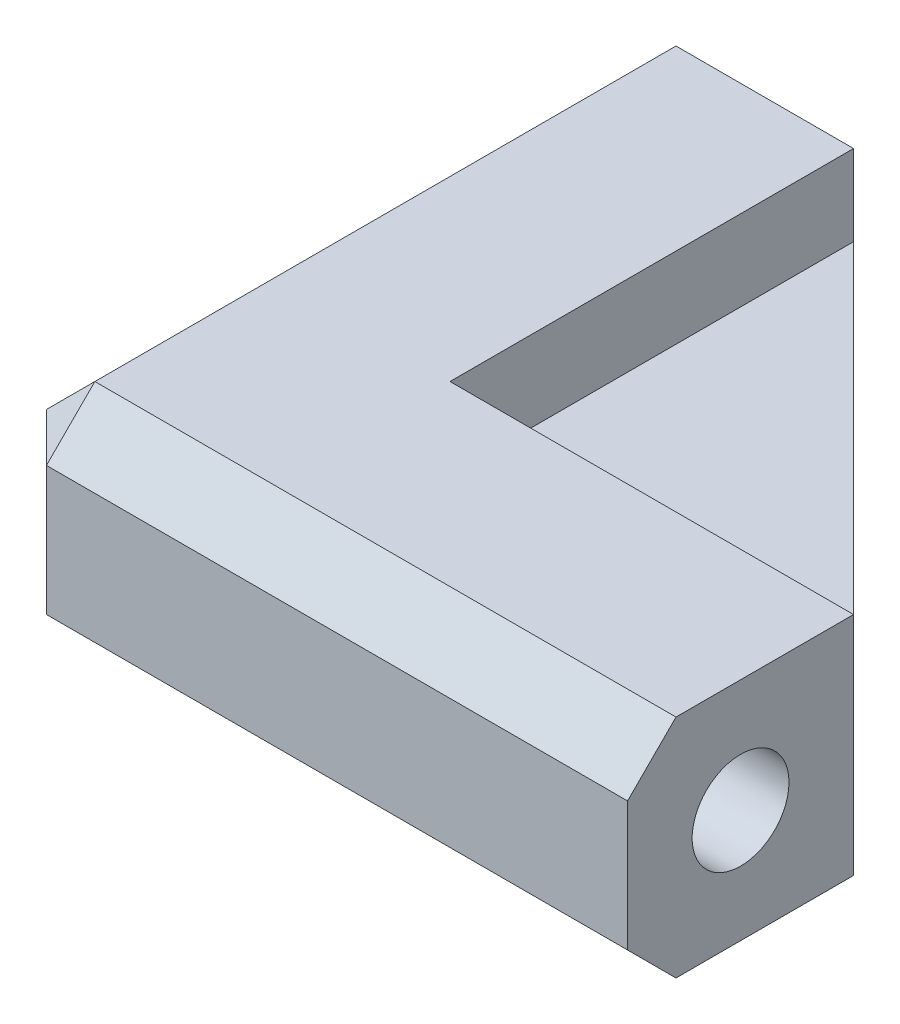
SolidWorks part; units mm, degrees
material "ABS"
ref_plane "Front" through (0, 0, 0) normal (0, 0, 1) x (1, 0, 0)
ref_plane "Top" through (0, 0, 0) normal (0, 1, 0) x (1, 0, 0)
ref_plane "Right" through (0, 0, 0) normal (1, 0, 0) x (0, 0, -1)
ref_axis "X" through (-80.9, 0, 0) along (1, 0, 0)
ref_axis "Y" through (0, -50, 0) along (0, 1, 0)
ref_axis "Z" through (0, 0, -80.9) along (0, 0, 1)
sketch "Sketch1" plane through (0, 0, 0) normal (0, 1, 0) x (1, 0, 0)
  line L0 (-3.5, 16) -> (-3.5, -3.5)
  line L1 (-3.5, -3.5) -> (16, -3.5)
  line L2 (16, -3.5) -> (16, 3.5)
  line L3 (16, 3.5) -> (3.5, 3.5)
  line L4 (3.5, 3.5) -> (3.5, 16)
  line L5 (3.5, 16) -> (-3.5, 16)
  line L6 (0, 16) -> (0, 0) construction
  line L7 (0, 0) -> (16, 0) construction
  dimension "D1" = 7
  dimension "D3" = 16
extrude "Boss-Extrude1" add sketch "Sketch1" along normal mid plane 7
sketch "Sketch2" plane through (0, 0, -16) normal (0, 0, -1) x (-1, 0, 0)
  circle A0 centre (0, 0) radius 1.5
  dimension "D1" = 3
extrude "Cut-Extrude1" cut sketch "Sketch2" against normal blind 14
sketch "Sketch3" plane through (16, 0, 0) normal (1, 0, 0) x (0, 0, -1)
  circle A0 centre (0, 0) radius 1.5
  dimension "D1" = 3
extrude "Cut-Extrude2" cut sketch "Sketch3" against normal blind 14
sketch "Sketch4" plane through (0, 0, 0) normal (0, 1, 0) x (1, 0, 0)
  line L0 (3.5, 16) -> (16, 3.5)
  line L1 (16, 3.5) -> (3.5, 3.5)
  line L2 (3.5, 3.5) -> (3.5, 16)
extrude "Boss-Extrude2" add sketch "Sketch4" along normal mid plane 2
chamfer "Chamfer1" distance 1.5 angle 45 5 edges at (6.25, -3.5, 3.5) (-3.5, -3.5, -6.25) (6.25, 3.5, 3.5) (-3.5, 3.5, -6.25) (-3.5, 0, 3.5)
